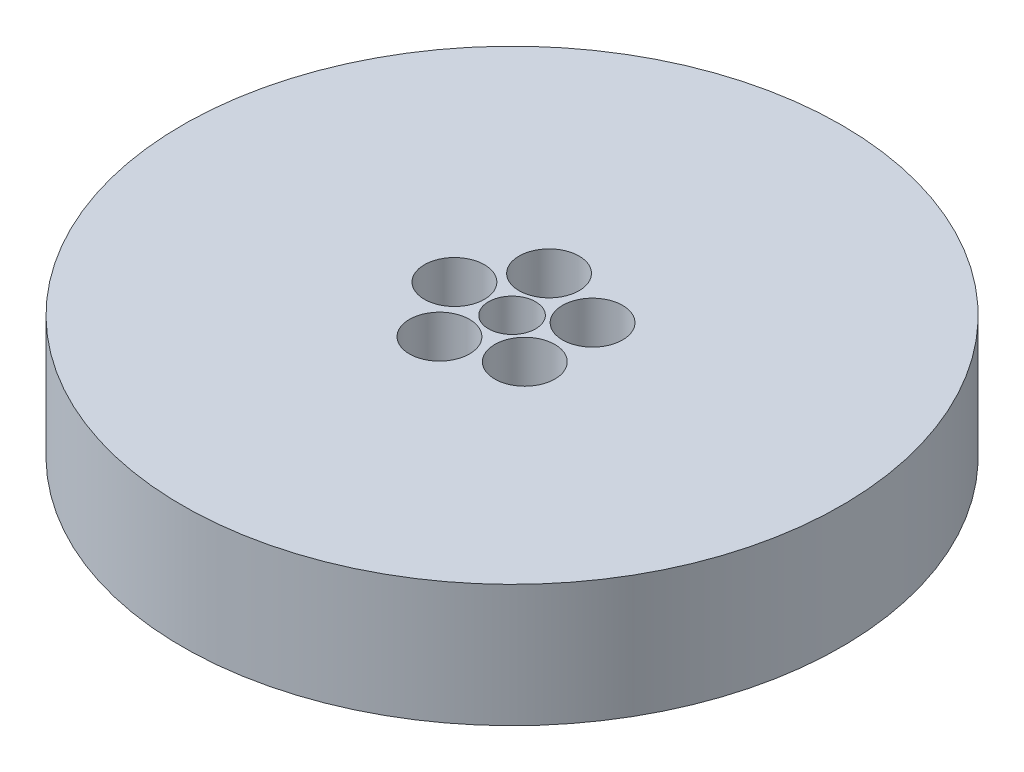
SolidWorks part; units mm, degrees
ref_plane "Front Plane" through (0, 0, 0) normal (0, 0, 1) x (1, 0, 0)
ref_plane "Top Plane" through (0, 0, 0) normal (0, 1, 0) x (1, 0, 0)
ref_plane "Right Plane" through (0, 0, 0) normal (1, 0, 0) x (0, 0, -1)
sketch "Sketch1" plane through (0, 0, 0) normal (0, 1, 0) x (1, 0, 0)
  circle A0 centre (0, 0) radius 70
  dimension "FLANGE_OD" = 140
extrude "Boss-Extrude1" add sketch "Sketch1" along normal blind 26
sketch "Sketch2" plane through (0, 0, 0) normal (0, 1, 0) x (1, 0, 0)
  circle A0 centre (0, 0) radius 5
  dimension "BORE_D" = 10
extrude "Cut-Extrude1" cut sketch "Sketch2" along normal through all
sketch "Sketch3" plane through (0, 26, 0) normal (0, 1, 0) x (1, 0, 0)
  circle A0 centre (0, 0) radius 12.239 construction
  circle A1 centre (-12.239, 0) radius 6.3781
  dimension "BOLT_D" = 12.7561
  dimension "BOLT_PCD" = 24.4781
extrude "Cut-Extrude2" cut sketch "Sketch3" against normal blind 16.1207
pattern_circular "CirPattern1" count 5 over 360 about axis through (0, 0, 0) along (0, 1, 0) of "Cut-Extrude2"
